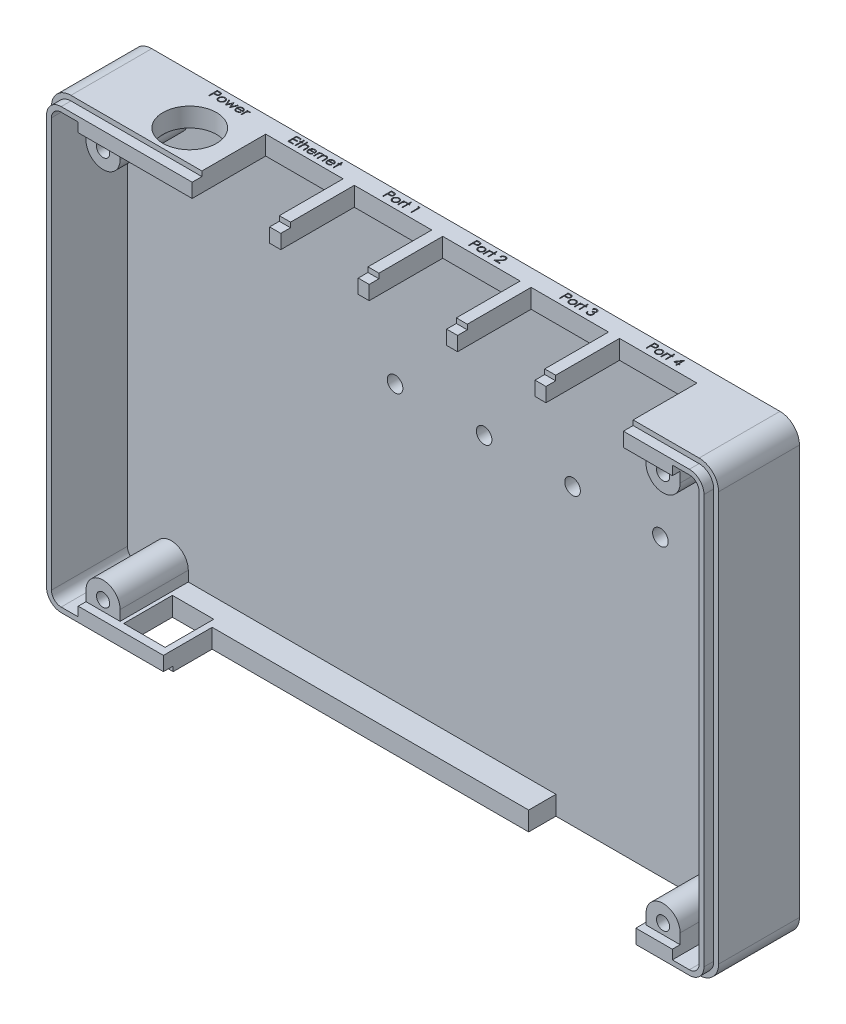
SolidWorks part; units mm, degrees
ref_plane "Front Plane" through (0, 0, 0) normal (0, 0, 1) x (1, 0, 0)
ref_plane "Top Plane" through (0, 0, 0) normal (0, 1, 0) x (1, 0, 0)
ref_plane "Right Plane" through (0, 0, 0) normal (1, 0, 0) x (0, 0, -1)
sketch "Sketch1" plane through (0, 0, 0) normal (0, 0, 1) x (1, 0, 0)
  line L1 (0, 0) -> (137, 0)
  line L2 (0, 0) -> (0, 92)
  line L3 (0, 92) -> (137, 92)
  line L4 (137, 0) -> (137, 92)
  dimension "D1" = 137
  dimension "D2" = 92
extrude "Boss-Extrude1" add sketch "Sketch1" along normal blind 2 and the other way blind 1
sketch "Sketch2" plane through (0, 0, 2) normal (0, 0, 1) x (1, 0, 0)
  line L1 (0, 92) -> (137, 92)
  line L2 (0, 92) -> (0, 0)
  line L3 (0, 0) -> (137, 0)
  line L4 (137, 92) -> (137, 0)
  line L5 (2, 2) -> (135, 2)
  line L6 (2, 2) -> (2, 90)
  line L7 (2, 90) -> (135, 90)
  line L8 (135, 2) -> (135, 90)
  dimension "D1" = 2
  dimension "D2" = 2
  dimension "D3" = 2
  dimension "D4" = 2
extrude "Boss-Extrude2" add sketch "Sketch2" along normal blind 15.6
sketch "Sketch3" plane through (0, 0, 17.6) normal (0, 0, 1) x (1, 0, 0)
  line L1 (0, 0) -> (137, 0)
  line L2 (0, 0) -> (0, 92)
  line L3 (0, 92) -> (137, 92)
  line L4 (137, 0) -> (137, 92)
  line L5 (1, 1) -> (136, 1)
  line L6 (1, 1) -> (1, 91)
  line L7 (1, 91) -> (136, 91)
  line L8 (136, 1) -> (136, 91)
  dimension "D1" = 1
  dimension "D2" = 1
  dimension "D3" = 1
  dimension "D4" = 1
extrude "Boss-Extrude3" add sketch "Sketch3" along normal blind 2
sketch "Sketch4" plane through (0, 0, 2) normal (0, 0, 1) x (1, 0, 0)
  line L0 (0, 0) -> (137, 0) construction
  line L1 (0, 92) -> (0, 0) construction
  line L2 (2, 2) -> (135, 2) construction
  line L4 (7.5, 6) -> (7.5, 2)
  line L5 (7.5, 2) -> (14.5, 2)
  line L6 (14.5, 6) -> (14.5, 2)
  line L7 (137, 0) -> (137, 92) construction
  line L8 (137, 92) -> (0, 92) construction
  line L9 (2, 2) -> (135, 2) construction
  line L11 (122.5, 6) -> (122.5, 2)
  line L12 (122.5, 2) -> (129.5, 2)
  line L13 (129.5, 6) -> (129.5, 2)
  line L14 (135, 90) -> (2, 90) construction
  line L16 (129.5, 86) -> (129.5, 90)
  line L17 (129.5, 90) -> (122.5, 90)
  line L18 (122.5, 86) -> (122.5, 90)
  line L19 (135, 90) -> (2, 90) construction
  line L21 (14.5, 86) -> (14.5, 90)
  line L22 (14.5, 90) -> (7.5, 90)
  line L23 (7.5, 86) -> (7.5, 90)
  arc A0 (14.5, 6) -> (7.5, 6) centre (11, 6) ccw
  circle A1 centre (11, 6) radius 1.35
  arc A2 (7.5, 86) -> (14.5, 86) centre (11, 86) ccw
  circle A3 centre (11, 86) radius 1.35
  arc A4 (122.5, 86) -> (129.5, 86) centre (126, 86) ccw
  circle A5 centre (126, 86) radius 1.35
  arc A6 (129.5, 6) -> (122.5, 6) centre (126, 6) ccw
  circle A7 centre (126, 6) radius 1.35
  dimension "D1" = 2.7
  dimension "D2" = 7
  dimension "D3" = 2.7
  dimension "D4" = 7
  dimension "D5" = 2.7
  dimension "D6" = 7
  dimension "D7" = 2.7
  dimension "D8" = 7
  dimension "D11" = 6
  dimension "D9" = 6
  dimension "D10" = 11
  dimension "D12" = 11
  dimension "D13" = 11
  dimension "D14" = 6
  dimension "D15" = 11
  dimension "D16" = 6
extrude "Boss-Extrude4" add sketch "Sketch4" along normal blind 15.6
sketch "Sketch8" plane through (0, 0, 2) normal (0, 0, 1) x (1, 0, 0)
  line L0 (122.5, 6) -> (122.5, 2) construction
  line L1 (14.5, 2) -> (122.5, 2)
  line L2 (14.5, 2) -> (14.5, 3.9)
  line L3 (14.5, 3.9) -> (122.5, 3.9)
  line L4 (122.5, 2) -> (122.5, 3.9)
  dimension "D1" = 1.9
extrude "Boss-Extrude6" add sketch "Sketch8" along normal blind 15.6
sketch "Sketch11" plane through (0, 0, 2) normal (0, 0, 1) x (1, 0, 0)
  line L0 (122.5, 90) -> (122.5, 86) construction
  line L1 (14.5, 90) -> (122.5, 90)
  line L2 (14.5, 90) -> (14.5, 88.1)
  line L3 (14.5, 88.1) -> (122.5, 88.1)
  line L4 (122.5, 90) -> (122.5, 88.1)
  dimension "D1" = 1.9
extrude "Boss-Extrude7" add sketch "Sketch11" along normal blind 15.6
sketch "Sketch14" plane through (0, 0, 19.6) normal (0, 0, 1) x (1, 0, 0)
  line L1 (0, 92) -> (137, 92)
  line L2 (0, 92) -> (0, 0)
  line L3 (0, 0) -> (137, 0)
  line L4 (137, 92) -> (137, 0)
  line L5 (1, 1) -> (136, 1)
  line L6 (1, 1) -> (1, 91)
  line L7 (1, 91) -> (136, 91)
  line L8 (136, 1) -> (136, 91)
extrude "Cut-Extrude5" cut sketch "Sketch14" against normal blind 4
fillet "Fillet1" radius 2 4 edges at (2, 2, 9.8) (135, 2, 9.8) (135, 90, 9.8) (2, 90, 9.8)
fillet "Fillet3" radius 3 4 edges at (1, 1, 16.6) (136, 1, 16.6) (136, 91, 16.6) (1, 91, 16.6)
fillet "Fillet4" radius 4 4 edges at (0, 92, 7.3) (137, 92, 7.3) (137, 0, 7.3) (0, 0, 7.3)
sketch "Sketch15" plane through (0, 92, 0) normal (0, 1, 0) x (1, 0, 0)
  line L0 (133, -15.6) -> (4, -15.6) construction
  line L1 (0, -15.6) -> (0, 1) construction
  circle A0 centre (22, -9.2) radius 5.5
  dimension "D1" = 11
  dimension "D2" = 6.4
  dimension "D3" = 22
extrude "Cut-Extrude6" cut sketch "Sketch15" against normal blind 4
sketch "Sketch16" plane through (0, 92, 0) normal (0, 1, 0) x (1, 0, 0)
  line L0 (0, -15.6) -> (0, 1) construction
  line L1 (30.9, -17.6) -> (46.8, -17.6)
  line L2 (30.9, -17.6) -> (30.9, -2.5)
  line L3 (30.9, -2.5) -> (46.8, -2.5)
  line L4 (46.8, -17.6) -> (46.8, -2.5)
  line L5 (133, -17.6) -> (4, -17.6) construction
  dimension "D1" = 30.9
  dimension "D2" = 0
  dimension "D3" = 15.1
  dimension "D4" = 15.9
extrude "Cut-Extrude7" cut sketch "Sketch16" against normal blind 4
sketch "Sketch17" plane through (0, 92, 0) normal (0, 1, 0) x (1, 0, 0)
  line L19 (133, -17.6) -> (46.8, -17.6) construction
  line L20 (49.1, -17.6) -> (65, -17.6)
  line L21 (49.1, -17.6) -> (49.1, -2.5)
  line L22 (49.1, -2.5) -> (65, -2.5)
  line L23 (65, -17.6) -> (65, -2.5)
  line L24 (67.25, -17.6) -> (83.15, -17.6)
  line L25 (67.25, -17.6) -> (67.25, -2.5)
  line L26 (67.25, -2.5) -> (83.15, -2.5)
  line L27 (83.15, -17.6) -> (83.15, -2.5)
  line L28 (85.4, -17.6) -> (101.3, -17.6)
  line L29 (85.4, -17.6) -> (85.4, -2.5)
  line L30 (85.4, -2.5) -> (101.3, -2.5)
  line L31 (101.3, -17.6) -> (101.3, -2.5)
  line L32 (103.55, -17.6) -> (119.45, -17.6)
  line L33 (103.55, -17.6) -> (103.55, -2.5)
  line L34 (103.55, -2.5) -> (119.45, -2.5)
  line L35 (119.45, -17.6) -> (119.45, -2.5)
  line L36 (0, -15.6) -> (0, 1) construction
  dimension "D1" = 15.1
  dimension "D2" = 15.9
  dimension "D3" = 15.9
  dimension "D4" = 15.1
  dimension "D5" = 15.9
  dimension "D6" = 15.1
  dimension "D7" = 15.9
  dimension "D8" = 15.1
  dimension "D9" = 0
  dimension "D10" = 0
  dimension "D11" = 0
  dimension "D12" = 49.1
  dimension "D13" = 67.25
  dimension "D14" = 85.4
  dimension "D15" = 103.55
  dimension "D16" = 0
extrude "Cut-Extrude8" cut sketch "Sketch17" against normal blind 4
sketch "Sketch19" plane through (0, 0, -1) normal (0, 0, -1) x (-1, 0, 0)
  circle A0 centre (-56.9642, 60.3523) radius 1.6
  circle A1 centre (-75.2522, 60.3523) radius 1.6
  circle A2 centre (-93.4132, 60.3523) radius 1.6
  circle A3 centre (-111.4472, 60.3523) radius 1.6
  dimension "D1" = 3.2
  dimension "D2" = 3.2
  dimension "D3" = 3.2
  dimension "D4" = 3.2
extrude "Cut-Extrude9" cut sketch "Sketch19" against normal blind 4
sketch "Sketch20" plane through (0, 0, 0) normal (0, -1, 0) x (1, 0, 0)
  line L0 (4, 17.6) -> (133, 17.6) construction
  line L1 (122, 17.6) -> (90, 17.6)
  line L2 (122, 17.6) -> (122, 2)
  line L3 (122, 2) -> (90, 2)
  line L4 (90, 17.6) -> (90, 2)
  line L5 (137, 15.6) -> (137, -1) construction
  dimension "D1" = 32
  dimension "D2" = 15.6
  dimension "D3" = 0
  dimension "D4" = 15
extrude "Cut-Extrude10" cut sketch "Sketch20" against normal blind 4
sketch "Sketch21" plane through (0, 0, 0) normal (0, -1, 0) x (1, 0, 0)
  line L1 (90, 17.6) -> (25, 17.6)
  line L2 (90, 17.6) -> (90, 7.6)
  line L3 (90, 7.6) -> (25, 7.6)
  line L4 (25, 17.6) -> (25, 7.6)
  dimension "D1" = 65
  dimension "D2" = 10
extrude "Cut-Extrude11" cut sketch "Sketch21" against normal blind 4
sketch "Sketch22" plane through (0, 0, 17.6) normal (0, 0, 1) x (1, 0, 0)
  line L1 (122.5, 88.1) -> (130.7778, 88.1)
  line L2 (122.5, 88.1) -> (122.5, 81.9328)
  line L3 (122.5, 81.9328) -> (130.7778, 81.9328)
  line L4 (130.7778, 88.1) -> (130.7778, 81.9328)
extrude "Cut-Extrude12" cut sketch "Sketch22" against normal blind 1.6
sketch "Sketch23" plane through (0, 0, 17.6) normal (0, 0, 1) x (1, 0, 0)
  line L1 (122.5, 3.9) -> (130.3517, 3.9)
  line L2 (122.5, 3.9) -> (122.5, 10.7356)
  line L3 (122.5, 10.7356) -> (130.3517, 10.7356)
  line L4 (130.3517, 3.9) -> (130.3517, 10.7356)
extrude "Cut-Extrude13" cut sketch "Sketch23" against normal blind 1.6
sketch "Sketch24" plane through (0, 0, 17.6) normal (0, 0, 1) x (1, 0, 0)
  line L1 (14.5, 3.9) -> (6.9446, 3.9)
  line L2 (14.5, 3.9) -> (14.5, 10.0585)
  line L3 (14.5, 10.0585) -> (6.9446, 10.0585)
  line L4 (6.9446, 3.9) -> (6.9446, 10.0585)
extrude "Cut-Extrude14" cut sketch "Sketch24" against normal blind 1.6
sketch "Sketch25" plane through (0, 0, 17.6) normal (0, 0, 1) x (1, 0, 0)
  line L1 (14.5, 88.1) -> (6.2877, 88.1)
  line L2 (14.5, 88.1) -> (14.5, 80.2964)
  line L3 (14.5, 80.2964) -> (6.2877, 80.2964)
  line L4 (6.2877, 88.1) -> (6.2877, 80.2964)
extrude "Cut-Extrude15" cut sketch "Sketch25" against normal blind 1.6
sketch "Sketch30" plane through (0, 92, 0) normal (0, 1, 0) x (1, 0, 0)
  text T0 "Ethernet" font "Century Gothic" height 1.8
extrude "Cut-Extrude17" cut sketch "Sketch30" against normal blind 0.5
sketch "Sketch31" plane through (0, 92, 0) normal (0, 1, 0) x (1, 0, 0)
  text T0 "Port 1" font "Century Gothic" height 1.8
extrude "Cut-Extrude18" cut sketch "Sketch31" against normal blind 0.5
sketch "Sketch32" plane through (0, 92, 0) normal (0, 1, 0) x (1, 0, 0)
  text T0 "Port 2" font "Century Gothic" height 1.8
extrude "Cut-Extrude19" cut sketch "Sketch32" against normal blind 0.5
sketch "Sketch33" plane through (0, 92, 0) normal (0, 1, 0) x (1, 0, 0)
  text T0 "Port 3" font "Century Gothic" height 1.8
extrude "Cut-Extrude20" cut sketch "Sketch33" against normal blind 0.5
sketch "Sketch34" plane through (0, 92, 0) normal (0, 1, 0) x (1, 0, 0)
  text T0 "Port 4" font "Century Gothic" height 1.8
extrude "Cut-Extrude21" cut sketch "Sketch34" against normal blind 0.5
sketch "Sketch35" plane through (0, 92, 0) normal (0, 1, 0) x (1, 0, 0)
  text T0 "Power" font "Century Gothic" height 1.8
extrude "Cut-Extrude22" cut sketch "Sketch35" against normal blind 0.5
sketch "Sketch36" plane through (0, 0, 0) normal (0, -1, 0) x (-1, 0, 0)
  line L6 (-15.2382, -16) -> (-23.7382, -16)
  line L7 (-15.2382, -16) -> (-15.2382, -6)
  line L8 (-15.2382, -6) -> (-23.7382, -6)
  line L9 (-23.7382, -16) -> (-23.7382, -6)
  dimension "D1" = 8.5
  dimension "D2" = 10
extrude "Cut-Extrude23" cut sketch "Sketch36" against normal blind 5
sketch "Sketch37" plane through (0, 0, 0) normal (0, -1, 0) x (-1, 0, 0)
  text T0 "1" font "Century Gothic" height 2
  text T1 "2" font "Century Gothic" height 2
  text T2 "3" font "Century Gothic" height 2
  text T3 "4" font "Century Gothic" height 2
  text T4 "5" font "Century Gothic" height 2
  text T5 "6" font "Century Gothic" height 2
  text T6 "7" font "Century Gothic" height 2
  text T7 "8" font "Century Gothic" height 2
  text T8 "9" font "Century Gothic" height 2
  text T9 "10" font "Century Gothic" height 2
  text T10 "11" font "Century Gothic" height 2
  text T11 "12" font "Century Gothic" height 2
  text T12 "13" font "Century Gothic" height 2
  text T13 "14" font "Century Gothic" height 2
  text T14 "15" font "Century Gothic" height 2
  text T15 "16" font "Century Gothic" height 2
  text T16 "UPS" font "Century Gothic" height 2
extrude "Cut-Extrude24" cut sketch "Sketch37" against normal blind 0.5
